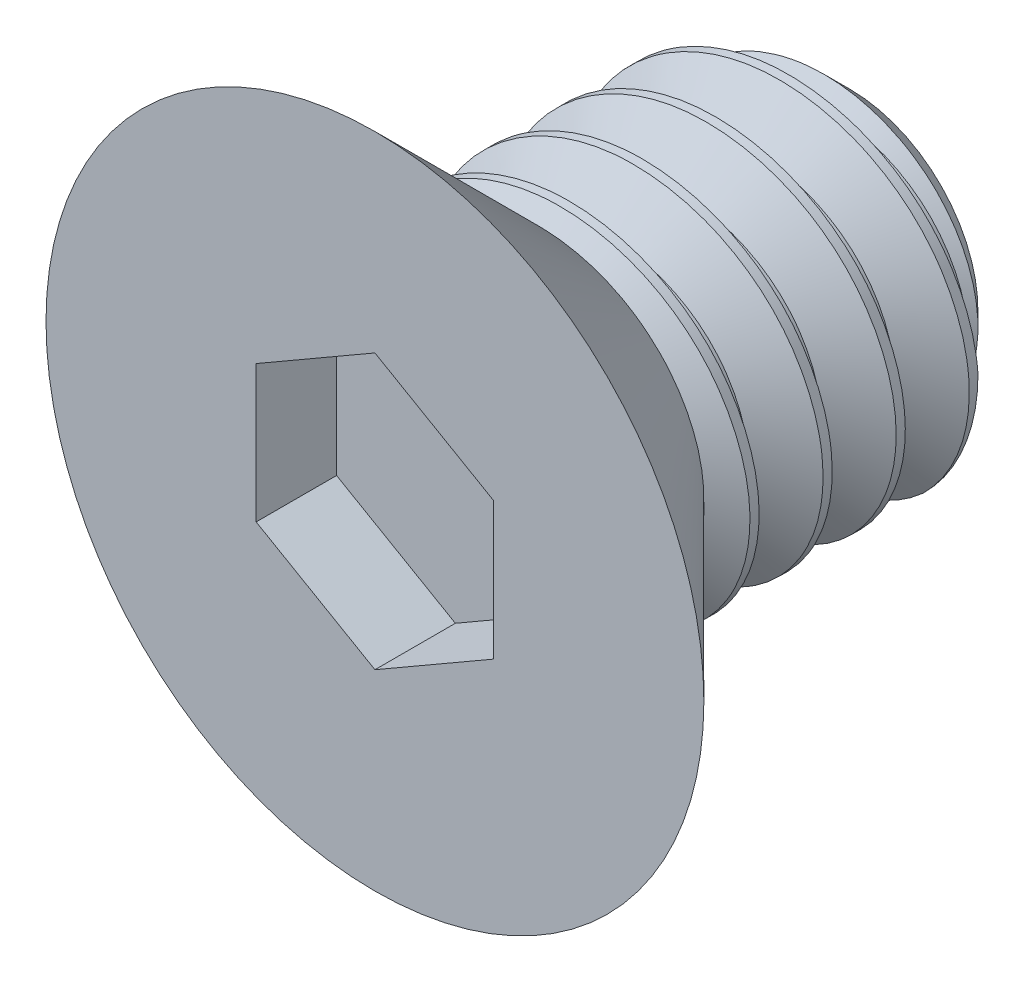
SolidWorks part; units mm, degrees
ref_plane "Front" through (0, 0, 0) normal (0, 0, 1) x (1, 0, 0)
ref_plane "Top" through (0, 0, 0) normal (0, 1, 0) x (1, 0, 0)
ref_plane "Right" through (0, 0, 0) normal (1, 0, 0) x (0, 0, -1)
sketch "Sketch1" plane through (0, 0, 0) normal (1, 0, 0) x (0, 0, -1)
  line L0 (0, 2) -> (0.2, 2) construction
  line L1 (0.2, 2) -> (1.2, 1) construction
  line L2 (0, 1) -> (3, 1)
  line L3 (3, 1) -> (3, 0)
  line L4 (3, 0) -> (0, 0)
  line L5 (0, 0) -> (0, 2) construction
  line L6 (0, 2) -> (0, -2) construction
  line L7 (3, 1) -> (3, -1) construction
  line L8 (0, -2) -> (0.2, -2) construction
  line L9 (0.2, -2) -> (1.2, -1) construction
  line L11 (0, 1) -> (0, 0)
  line L12 (1.2, 1) -> (1.2, 0) construction
  point P12 (0, 0)
revolve "Revolve1" add sketch "Sketch1" angle 360 mid plane about L4
sketch "Sketch3" plane through (0, 0, -3) normal (0, 0, -1) x (-1, 0, 0)
  circle A0 centre (0, 0) radius 1
curve "Helix/Spiral1" pitch 0.4 height 3 radius 1 centre (0, 0, -3) axis (0, 0, 1) start towards (0, 1, 0)
sketch "Sketch2" plane through (0, 0, 0) normal (1, 0, 0) x (0, 0, -1)
  line L0 (3, 1) -> (3.35, 1)
  line L1 (3.35, 1) -> (3.2, 0.7402)
  line L2 (3.2, 0.7402) -> (3.15, 0.7402)
  line L3 (3.15, 0.7402) -> (3, 1)
  line L4 (3.075, 0.8701) -> (3.275, 0.8701) construction
  dimension "D1" = 60
  dimension "D2" = 0.05
  dimension "D3" = 0.2
chamfer "Chamfer1" distance 0.3 angle 45 1 edges at (0, 1, -3)
sweep "Cut-Sweep1" cut profiles "Sketch2" path "Helix/Spiral1" align with end faces yes
sketch "Sketch7" plane through (0, 0, 0) normal (1, 0, 0) x (0, 0, -1)
  line L0 (0, 2) -> (0.2, 2) construction
  line L1 (0.2, 2) -> (1.2, 1) construction
  line L2 (0, 2) -> (0.2, 2)
  line L3 (0.2, 2) -> (1.2, 1)
  line L4 (1.2, 1) -> (1.2, 0) construction
  line L5 (1.2, 1) -> (1.2, 0)
  line L7 (0, 0) -> (0, 2) construction
  line L8 (0, 0) -> (0, 2)
  line L9 (0, 0) -> (1.2, 0)
  line L10 (2.2, 0) -> (-2.2, 0) construction
revolve "Revolve2" add sketch "Sketch7" angle 360 mid plane about L9
ref_plane "Plane1" through (0, 0, -1.2) normal (0, 0, 1) x (1, 0, 0)
sketch "Sketch8" plane through (0, 0, -1.2) normal (0, 0, 1) x (1, 0, 0)
  circle A0 centre (0, 0) radius 1
extrude "Boss-Extrude1" add sketch "Sketch8" against normal through all draft 45
sketch "Sketch5" plane through (0, 0, 0) normal (0, 0, 1) x (1, 0, 0)
  line L1 (0.65, -0.3753) -> (0.65, 0.3753)
  line L2 (0.65, 0.3753) -> (0, 0.7506)
  line L3 (0, 0.7506) -> (-0.65, 0.3753)
  line L4 (-0.65, 0.3753) -> (-0.65, -0.3753)
  line L5 (-0.65, -0.3753) -> (0, -0.7506)
  line L6 (0, -0.7506) -> (0.65, -0.3753)
  circle A0 centre (0, 0) radius 0.65 construction
  dimension "Hex" = 1.3
extrude "Cut-Extrude2" cut sketch "Sketch5" against normal blind 0.84
sketch "Sketch6" plane through (0, 0, 0) normal (0, 0, 1) x (1, 0, 0)
  circle A0 centre (0, 0) radius 0.7506
extrude "Cut-Extrude3" cut sketch "Sketch6" against normal blind 0.84 draft 45
sketch "Sketch9" [suppressed] plane through (0, 0, -5.5) normal (0, 0, 1) x (1, 0, 0)
  circle A1 centre (0, 0) radius 5
  circle A2 centre (0, 0) radius 5
  point P0 (0, 5)
  dimension "D1" = 0
extrude "Boss-Extrude2" [suppressed] add sketch "Sketch9" against normal offset from surface (18.5 mm away) 26 up to face at (0, 0.7, -3)
fillet "Fillet1" [suppressed] radius 0.2
sketch "Sketch10" plane through (0, 0, 0) normal (1, 0, 0) x (0, 0, -1)
  line L0 (3, 1) -> (3, -1) construction
  point P0 (2.4, -1)
  dimension "D1" = 0.6
sketch "Sketch11" plane through (0, 0, 0) normal (1, 0, 0) x (0, 0, -1)
  line L0 (3, 0) -> (0, 0) construction
  line L1 (0.4, 0) -> (0, 0)
  line L2 (0.4, 0) -> (0.4, 2)
  line L3 (0.4, 2) -> (0, 2)
  line L4 (0, 0) -> (0, 2)
  point P6 (0, 2)
  dimension "D1" = 2.6
revolve "Cut-Revolve1" cut sketch "Sketch11" angle 360 about L4
equation "\"D3@Helix/Spiral1\" = \"Lg@Sketch1\""
equation "\"D2@Sketch2\" = \"D4@Helix/Spiral1\" * .125"
equation "\"D3@Sketch2\" = \"D4@Helix/Spiral1\" * .5"
equation "\"D1@Chamfer1\" = \"D4@Helix/Spiral1\" * .75"
equation "\"D1@Cut-Extrude2\" = \"Head Ht@Sketch1\" * .7"
equation "\"D1@Sketch10\" = \"D4@Helix/Spiral1\" * 1.5"
equation "\"D1@Cut-Extrude3\" = \"D1@Cut-Extrude2\""
equation "\"D1@Fillet1\" = \"Dia@Sketch1\" * .1"
